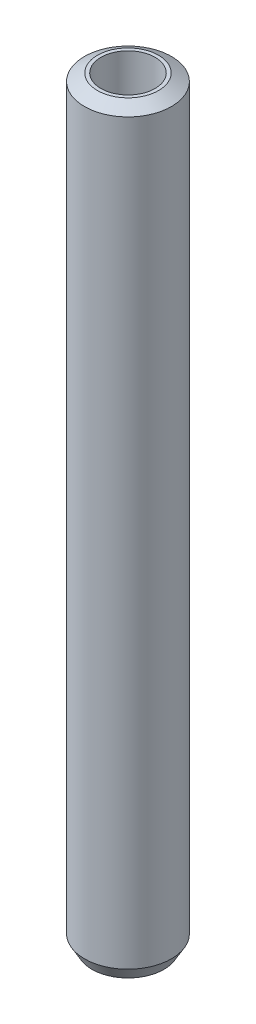
SolidWorks part; units mm, degrees
ref_plane "Front Plane" through (0, 0, 0) normal (0, 0, 1) x (1, 0, 0)
ref_plane "Top Plane" through (0, 0, 0) normal (0, 1, 0) x (1, 0, 0)
ref_plane "Right Plane" through (0, 0, 0) normal (1, 0, 0) x (0, 0, -1)
sketch "Sketch1" plane through (0, 0, 0) normal (0, 1, 0) x (1, 0, 0)
  circle A0 centre (0, 0) radius 32.5
  dimension "SHAFT_OD" = 65
extrude "Boss-Extrude1" add sketch "Sketch1" along normal blind 567.1533
sketch "Sketch2" plane through (0, 0, 0) normal (0, 1, 0) x (1, 0, 0)
  circle A0 centre (0, 0) radius 20.2496
  dimension "BORE_D" = 40.4991
extrude "Cut-Extrude1" cut sketch "Sketch2" along normal through all
chamfer "Chamfer1" distance 5.5566 angle 60 2 edges at (0, 567.1533, 32.5) (0, 0, 32.5) first distance on face at (0, 567.1533, 32.5) first distance on face at (0, 0, 20.2496)
